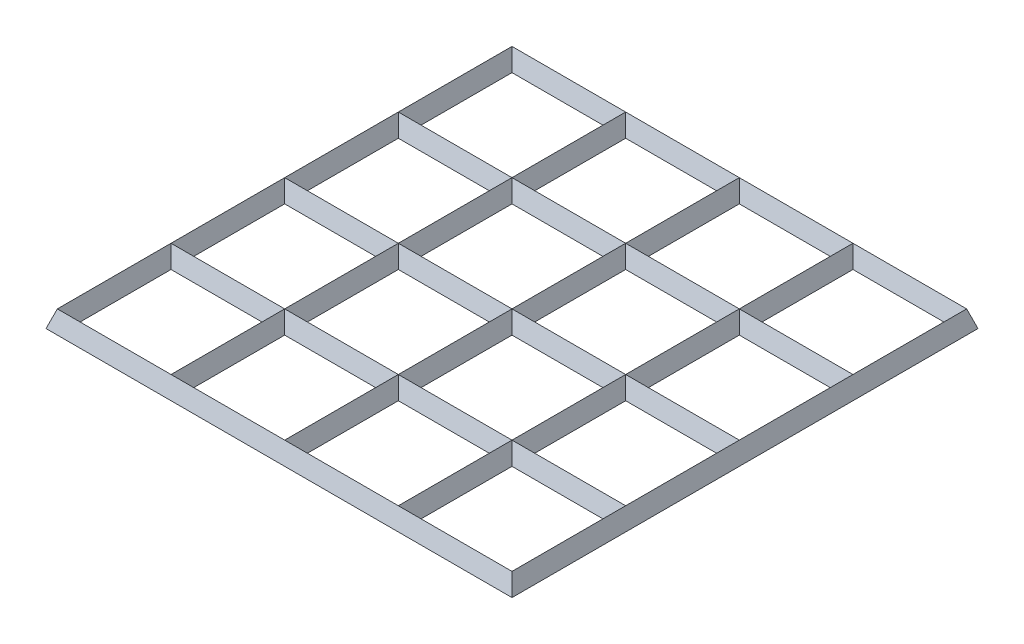
SolidWorks part; units mm, degrees
ref_plane "前视基准面" through (0, 0, 0) normal (0, 0, 1) x (1, 0, 0)
ref_plane "上视基准面" through (0, 0, 0) normal (0, 1, 0) x (1, 0, 0)
ref_plane "右视基准面" through (0, 0, 0) normal (1, 0, 0) x (0, 0, -1)
sketch "草图1" plane through (0, 0, 0) normal (0, 1, 0) x (1, 0, 0)
  line L0 (-2000, 0) -> (2000, 0)
  line L1 (-2000, 2000) -> (2000, 2000)
  line L2 (-2000, 2000) -> (-2000, -2000)
  line L3 (-2000, -2000) -> (2000, -2000)
  line L4 (2000, 2000) -> (2000, -2000)
  line L5 (-2000, 2000) -> (2000, -2000) construction
  line L6 (-2000, -2000) -> (2000, 2000) construction
  line L7 (0, 2000) -> (0, -2000)
  line L8 (-2000, 1000) -> (2000, 1000)
  line L9 (-2000, -1000) -> (2000, -1000)
  line L10 (-1000, 2000) -> (-1000, -2000)
  line L11 (1000, 2000) -> (1000, -2000)
  point P0 (0, 0)
  dimension "D1" = 4000
  dimension "D2" = 4000
  dimension "D3" = 1000
  dimension "D4" = 1000
  dimension "D5" = 1000
  dimension "D6" = 1000
extrude "拉伸-薄壁1" add sketch "草图1" along normal blind 150 thin contours L3 L4 L1 L2 | L10 | L9 | L0 | L8 | L7 | L11 thin type mid plane wall 100
chamfer "倒角1" distance 150 distance2 50 17 edges at (1950, 150, -1500) (1950, 150, -500) (1950, 150, 500) (1950, 150, 1500) (950, 150, 1500) (950, 150, 500) (950, 150, -500) (950, 150, -1500) (-50, 150, -1500) (-50, 150, -500) (-50, 150, 500) (-50, 150, 1500) (-1050, 150, 1500) (-1050, 150, 500) (-1050, 150, -500) (-1050, 150, -1500) (-2050, 150, 0)
chamfer "倒角2" distance 50 distance2 150 17 edges at (-1950, 150, -1500) (-1950, 150, -500) (-1950, 150, 500) (-1950, 150, 1500) (-950, 150, 1500) (-950, 150, 500) (-950, 150, -500) (-950, 150, -1500) (50, 150, -1500) (50, 150, -500) (50, 150, 500) (50, 150, 1500) (1050, 150, 1500) (1050, 150, 500) (1050, 150, -500) (1050, 150, -1500) (2050, 150, 0)
chamfer "倒角3" distance 50 distance2 150 17 edges at (-1500, 150, 1950) (-500, 150, 1950) (500, 150, 1950) (1500, 150, 1950) (1500, 150, 950) (500, 150, 950) (-500, 150, 950) (-1500, 150, 950) (1500, 150, -50) (500, 150, -50) (-500, 150, -50) (-1500, 150, -50) (1500, 150, -1050) (500, 150, -1050) (-500, 150, -1050) (-1500, 150, -1050) (0, 150, -2050)
chamfer "倒角4" distance 150 distance2 50 51 edges at (-1500, 150, 1050) (-500, 150, 1050) (500, 150, 1050) (1500, 150, 1050) (-1500, 150, 50) (-500, 150, 50) (500, 150, 50) (1500, 150, 50) (-1500, 150, -950) (-500, 150, -950) (500, 150, -950) (1500, 150, -950) (-1500, 150, -1950) (-500, 150, -1950) (500, 150, -1950) (1500, 150, -1950) (0, 150, 2050) (-2025, 75, 2050) (1975, 75, -1950) (1975, 75, -950) (1975, 75, 50) (1975, 75, 1050) (975, 75, 1050) (975, 75, 50) (975, 75, -950) (975, 75, -1950) (-25, 75, -1950) (-25, 75, -950) (-25, 75, 50) (-25, 75, 1050) (-1025, 75, 1050) (-1025, 75, 50) (-1025, 75, -950) (-1025, 75, -1950) (2025, 75, 2050) (-1975, 75, -1950) (-1975, 75, -950) (-1975, 75, 50) (-1975, 75, 1050) (-975, 75, 1050) (-975, 75, 50) (-975, 75, -950) (-975, 75, -1950) (25, 75, -1950) (25, 75, -950) (25, 75, 50) (25, 75, 1050) (1025, 75, 1050) (1025, 75, 50) (1025, 75, -950) (1025, 75, -1950)
